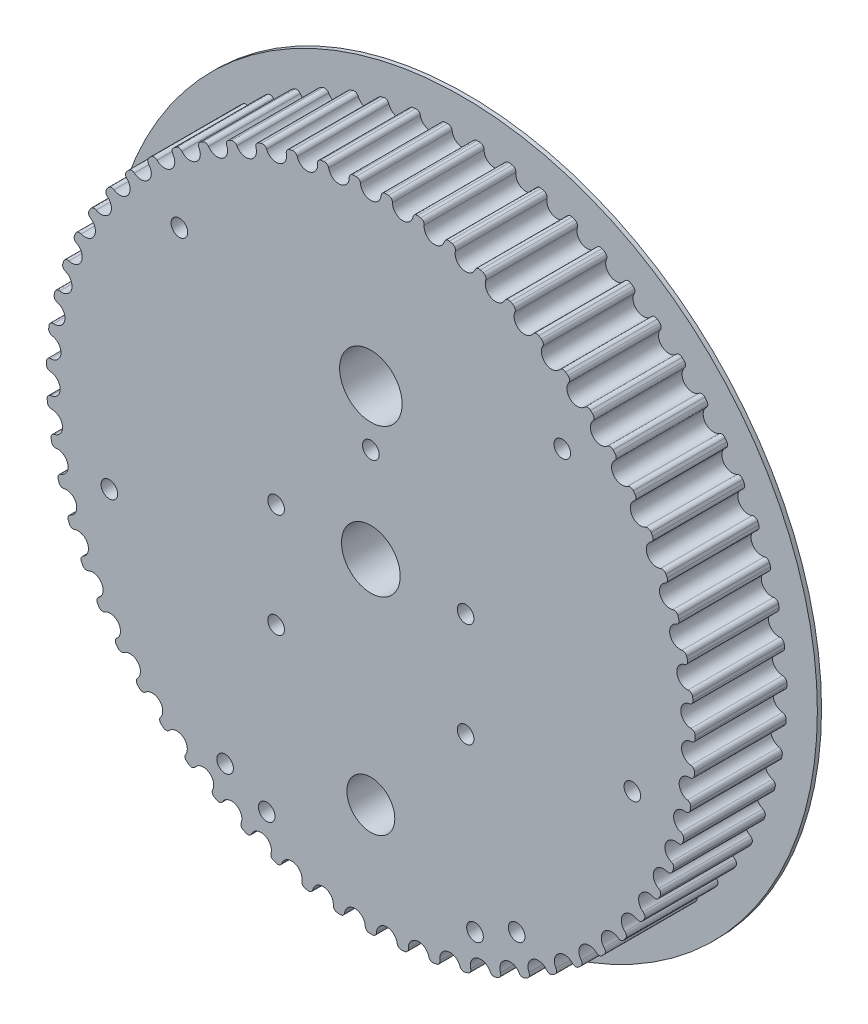
SolidWorks part; units mm, degrees
material "PETG"
ref_plane "Front Plane" through (0, 0, 0) normal (0, 0, 1) x (1, 0, 0)
ref_plane "Top Plane" through (0, 0, 0) normal (0, 1, 0) x (1, 0, 0)
ref_plane "Right Plane" through (0, 0, 0) normal (1, 0, 0) x (0, 0, -1)
sketch "Sketch1" plane through (0, 0, 0) normal (0, 0, 1) x (1, 0, 0)
  line L0 (0, 0) -> (0, 50000) construction
  line L1 (0, 0) -> (3.9983, 80.1144) construction
  line L2 (0, 0) -> (-3.9983, 80.1144) construction
  circle A0 centre (0, 0) radius 80.2141 construction
  arc A1 (-2.4815, 76.9081) -> (2.4815, 76.9081) centre (0, 77.1141) ccw
  arc A2 (3.8832, 77.8073) -> (-3.8832, 77.8073) centre (0, 0) ccw construction
  arc A3 (-2.4815, 76.9081) -> (-3.5233, 77.8244) centre (-3.478, 76.8254) ccw
  arc A4 (3.5233, 77.8244) -> (2.4815, 76.9081) centre (3.478, 76.8254) ccw
  arc A5 (-3.5233, 77.8244) -> (-3.8832, 77.8073) centre (0, 0) ccw
  arc A6 (3.5233, 77.8244) -> (3.8832, 77.8073) centre (0, 0) cw
  arc A7 (4.243, 77.7885) -> (3.8832, 77.8073) centre (0, 0) ccw
  arc A8 (5.1884, 76.773) -> (4.243, 77.7885) centre (4.1886, 76.7899) ccw
  arc A9 (5.1884, 76.773) -> (10.1267, 76.2789) centre (7.6781, 76.7309) ccw
  arc A10 (11.2546, 77.0868) -> (10.1267, 76.2789) centre (11.1101, 76.0973) ccw
  arc A11 (11.2546, 77.0868) -> (11.611, 77.034) centre (0, 0) cw
  arc A12 (11.9672, 76.9794) -> (11.611, 77.034) centre (0, 0) ccw
  arc A13 (12.8068, 75.8749) -> (11.9672, 76.9794) centre (11.8136, 75.9913) ccw
  arc A14 (12.8068, 75.8749) -> (17.6713, 74.8915) centre (15.2799, 75.5851) ccw
  arc A15 (18.874, 75.5832) -> (17.6713, 74.8915) centre (18.6317, 74.613) ccw
  arc A16 (18.874, 75.5832) -> (19.2234, 75.4951) centre (0, 0) cw
  arc A17 (19.5724, 75.4054) -> (19.2234, 75.4951) centre (0, 0) ccw
  arc A18 (20.2978, 74.2227) -> (19.5724, 75.4054) centre (19.3212, 74.4374) ccw
  arc A19 (20.2978, 74.2227) -> (25.0403, 72.7599) centre (22.7298, 73.6881) ccw
  arc A20 (26.3059, 73.3284) -> (25.0403, 72.7599) centre (25.9682, 72.3871) ccw
  arc A21 (26.3059, 73.3284) -> (26.6448, 73.2059) centre (0, 0) cw
  arc A22 (26.9831, 73.0819) -> (26.6448, 73.2059) centre (0, 0) ccw
  arc A23 (27.5872, 71.8329) -> (26.9831, 73.0819) centre (26.6367, 72.1438) ccw
  arc A24 (27.5872, 71.8329) -> (32.1604, 69.9051) centre (29.9538, 71.0588) ccw
  arc A25 (33.4763, 70.3448) -> (32.1604, 69.9051) centre (33.0466, 69.4418) ccw
  arc A26 (33.4763, 70.3448) -> (33.8013, 70.1892) centre (0, 0) cw
  arc A27 (34.1256, 70.0321) -> (33.8013, 70.1892) centre (0, 0) ccw
  arc A28 (34.6023, 68.7291) -> (34.1256, 70.0321) centre (33.6876, 69.1331) ccw
  arc A29 (34.6023, 68.7291) -> (38.9609, 66.3556) centre (36.8801, 67.7233) ccw
  arc A30 (40.314, 66.662) -> (38.9609, 66.3556) centre (39.7965, 65.8063) ccw
  arc A31 (40.314, 66.662) -> (40.6219, 66.4749) centre (0, 0) cw
  arc A32 (40.929, 66.2862) -> (40.6219, 66.4749) centre (0, 0) ccw
  arc A33 (41.2736, 64.9423) -> (40.929, 66.2862) centre (40.4036, 65.4354) ccw
  arc A34 (41.2736, 64.9423) -> (45.3742, 62.1466) centre (43.4399, 63.7147) ccw
  arc A35 (46.7511, 62.3168) -> (45.3742, 62.1466) centre (46.151, 61.5169) ccw
  arc A36 (46.7511, 62.3168) -> (47.0388, 62.0999) centre (0, 0) cw
  arc A37 (47.3256, 61.8816) -> (47.0388, 62.0999) centre (0, 0) ccw
  arc A38 (47.5347, 60.5101) -> (47.3256, 61.8816) centre (46.7181, 61.0873) ccw
  arc A39 (47.5347, 60.5101) -> (51.3365, 57.32) centre (49.568, 59.0728) ccw
  arc A40 (52.7235, 57.3522) -> (51.3365, 57.32) centre (52.0467, 56.616) ccw
  arc A41 (52.7235, 57.3522) -> (52.9882, 57.1077) centre (0, 0) cw
  arc A42 (53.2518, 56.862) -> (52.9882, 57.1077) centre (0, 0) ccw
  arc A43 (53.3233, 55.4765) -> (53.2518, 56.862) centre (52.5683, 56.1321) ccw
  arc A44 (53.3233, 55.4765) -> (56.7886, 51.9237) centre (55.2034, 53.8439) ccw
  arc A45 (58.172, 51.8177) -> (56.7886, 51.9237) centre (57.4253, 51.1525) ccw
  arc A46 (58.172, 51.8177) -> (58.411, 51.548) centre (0, 0) cw
  arc A47 (58.6488, 51.2773) -> (58.411, 51.548) centre (0, 0) ccw
  arc A48 (58.582, 49.8915) -> (58.6488, 51.2773) centre (57.896, 50.6191) ccw
  arc A49 (58.582, 49.8915) -> (61.6764, 46.0113) centre (60.2902, 48.0798) ccw
  arc A50 (63.0423, 45.7681) -> (61.6764, 46.0113) centre (62.233, 45.1806) ccw
  arc A51 (63.0423, 45.7681) -> (63.2533, 45.476) centre (0, 0) cw
  arc A52 (63.463, 45.183) -> (63.2533, 45.476) centre (0, 0) ccw
  arc A53 (63.2585, 43.8107) -> (63.463, 45.183) centre (62.6483, 44.603) ccw
  arc A54 (63.2585, 43.8107) -> (65.9511, 39.6417) centre (64.7778, 41.838) ccw
  arc A55 (67.286, 39.2637) -> (65.9511, 39.6417) centre (66.4223, 38.7597) ccw
  arc A56 (67.286, 39.2637) -> (67.4669, 38.952) centre (0, 0) cw
  arc A57 (67.6464, 38.6396) -> (67.4669, 38.952) centre (0, 0) ccw
  arc A58 (67.3063, 37.2945) -> (67.6464, 38.6396) centre (66.778, 38.1436) ccw
  arc A59 (67.3063, 37.2945) -> (69.5704, 32.8781) centre (68.6217, 35.1803) ccw
  arc A60 (70.8611, 32.3691) -> (69.5704, 32.8781) centre (69.9515, 31.9536) ccw
  arc A61 (70.8611, 32.3691) -> (71.01, 32.0409) centre (0, 0) cw
  arc A62 (71.1575, 31.7122) -> (71.01, 32.0409) centre (0, 0) ccw
  arc A63 (70.6852, 30.4076) -> (71.1575, 31.7122) centre (70.2441, 31.3051) ccw
  arc A64 (70.6852, 30.4076) -> (72.4983, 25.7878) centre (71.7835, 28.1729) ccw
  arc A65 (73.7319, 25.1527) -> (72.4983, 25.7878) centre (72.7854, 24.8299) ccw
  arc A66 (73.7319, 25.1527) -> (73.8474, 24.8114) centre (0, 0) cw
  arc A67 (73.9614, 24.4696) -> (73.8474, 24.8114) centre (0, 0) ccw
  arc A68 (73.3615, 23.2186) -> (73.9614, 24.4696) centre (73.012, 24.1555) ccw
  arc A69 (73.3615, 23.2186) -> (74.7057, 18.4411) centre (74.2319, 20.8856) ccw
  arc A70 (75.8699, 17.6864) -> (74.7057, 18.4411) centre (74.896, 17.4594) ccw
  arc A71 (75.8699, 17.6864) -> (75.9509, 17.3353) centre (0, 0) cw
  arc A72 (76.0302, 16.9838) -> (75.9509, 17.3353) centre (0, 0) ccw
  arc A73 (75.3088, 15.7987) -> (76.0302, 16.9838) centre (75.0543, 16.7658) ccw
  arc A74 (75.3088, 15.7987) -> (76.1706, 10.9112) centre (75.9426, 13.3907) ccw
  arc A75 (77.2539, 10.0443) -> (76.1706, 10.9112) centre (76.2622, 9.9154) ccw
  arc A76 (77.2539, 10.0443) -> (77.2995, 9.6869) centre (0, 0) cw
  arc A77 (77.3435, 9.3292) -> (77.2995, 9.6869) centre (0, 0) ccw
  arc A78 (76.5076, 8.2219) -> (77.3435, 9.3292) centre (76.3507, 9.2095) ccw
  arc A79 (76.5076, 8.2219) -> (76.8785, 3.2728) centre (76.8985, 5.7627) ccw
  arc A80 (77.8701, 2.3024) -> (76.8785, 3.2728) centre (76.8705, 2.2729) ccw
  arc A81 (77.8701, 2.3024) -> (77.8799, 1.9422) centre (0, 0) cw
  arc A82 (77.888, 1.582) -> (77.8799, 1.9422) centre (0, 0) ccw
  arc A83 (76.9461, 0.5633) -> (77.888, 1.582) centre (76.8882, 1.5616) ccw
  arc A84 (76.9461, 0.5633) -> (76.8224, -4.3981) centre (77.0901, -1.9225) ccw
  arc A85 (77.7124, -5.4624) -> (76.8224, -4.3981) centre (76.7148, -5.3923) ccw
  arc A86 (77.7124, -5.4624) -> (77.6863, -5.8218) centre (0, 0) cw
  arc A87 (77.6585, -6.181) -> (77.6863, -5.8218) centre (0, 0) ccw
  arc A88 (76.6198, -7.1008) -> (77.6585, -6.181) centre (76.6616, -6.1017) ccw
  arc A89 (76.6198, -7.1008) -> (76.0027, -12.0252) centre (76.5156, -9.5887) ccw
  arc A90 (76.7823, -13.1729) -> (76.0027, -12.0252) centre (75.7967, -13.0038) ccw
  arc A91 (76.7823, -13.1729) -> (76.7206, -13.5279) centre (0, 0) cw
  arc A92 (76.6572, -13.8826) -> (76.7206, -13.5279) centre (0, 0) ccw
  arc A93 (75.5321, -14.6944) -> (76.6572, -13.8826) centre (75.6732, -13.7044) ccw
  arc A94 (75.5321, -14.6944) -> (74.4277, -19.5329) centre (75.1807, -17.1595) ccw
  arc A95 (75.0892, -20.7525) -> (74.4277, -19.5329) centre (74.1253, -20.4861) ccw
  arc A96 (75.0892, -20.7525) -> (74.9924, -21.0996) centre (0, 0) cw
  arc A97 (74.894, -21.4462) -> (74.9924, -21.0996) centre (0, 0) ccw
  arc A98 (73.6936, -22.142) -> (74.894, -21.4462) centre (73.9326, -21.1709) ccw
  arc A99 (73.6936, -22.142) -> (72.113, -26.8465) centre (73.0986, -24.5598) ccw
  arc A100 (72.6497, -28.1258) -> (72.113, -26.8465) centre (71.7172, -27.7648) ccw
  arc A101 (72.6497, -28.1258) -> (72.5189, -28.4616) centre (0, 0) cw
  arc A102 (72.3865, -28.7967) -> (72.5189, -28.4616) centre (0, 0) ccw
  arc A103 (71.1228, -29.3694) -> (72.3865, -28.7967) centre (71.4573, -28.427) ccw
  arc A104 (71.1228, -29.3694) -> (69.0816, -33.8932) centre (70.2899, -31.716) ccw
  arc A105 (69.4883, -35.2196) -> (69.0816, -33.8932) centre (68.5963, -34.7676) ccw
  arc A106 (69.4883, -35.2196) -> (69.3247, -35.5407) centre (0, 0) cw
  arc A107 (69.1595, -35.861) -> (69.3247, -35.5407) centre (0, 0) ccw
  arc A108 (67.8451, -36.305) -> (69.1595, -35.861) centre (68.2718, -35.4006) ccw
  arc A109 (67.8451, -36.305) -> (65.3637, -40.6031) centre (66.7828, -38.557) ccw
  arc A110 (65.6363, -41.9634) -> (65.3637, -40.6031) centre (64.7937, -41.4248) ccw
  arc A111 (65.6363, -41.9634) -> (65.4415, -42.2666) centre (0, 0) cw
  arc A112 (65.2453, -42.5688) -> (65.4415, -42.2666) centre (0, 0) ccw
  arc A113 (63.8932, -42.8798) -> (65.2453, -42.5688) centre (64.4077, -42.0224) ccw
  arc A114 (63.8932, -42.8798) -> (60.9961, -46.9094) centre (62.6119, -45.0149) ccw
  arc A115 (61.1319, -48.2902) -> (60.9961, -46.9094) centre (60.3472, -47.6703) ccw
  arc A116 (61.1319, -48.2902) -> (60.9079, -48.5724) centre (0, 0) cw
  arc A117 (60.6826, -48.8536) -> (60.9079, -48.5724) centre (0, 0) ccw
  arc A118 (59.3062, -49.0285) -> (60.6826, -48.8536) centre (59.9036, -48.2265) ccw
  arc A119 (59.3062, -49.0285) -> (56.0223, -52.7496) centre (57.8187, -51.0253) ccw
  arc A120 (56.02, -54.137) -> (56.0223, -52.7496) centre (55.3009, -53.442) ccw
  arc A121 (56.02, -54.137) -> (55.769, -54.3955) centre (0, 0) cw
  arc A122 (55.5168, -54.6529) -> (55.769, -54.3955) centre (0, 0) ccw
  arc A123 (54.1299, -54.6898) -> (55.5168, -54.6529) centre (54.8041, -53.9513) ccw
  arc A124 (54.1299, -54.6898) -> (50.4918, -58.0655) centre (52.4509, -56.5286) ccw
  arc A125 (50.3513, -59.4457) -> (50.4918, -58.0655) centre (49.705, -58.6827) ccw
  arc A126 (50.3513, -59.4457) -> (50.0758, -59.678) centre (0, 0) cw
  arc A127 (49.7992, -59.909) -> (50.0758, -59.678) centre (0, 0) ccw
  arc A128 (48.4155, -59.8076) -> (49.7992, -59.909) centre (49.16, -59.14) ccw
  arc A129 (48.4155, -59.8076) -> (44.4594, -62.8043) centre (46.5618, -61.4701) ccw
  arc A130 (44.1822, -64.1637) -> (44.4594, -62.8043) centre (43.6151, -63.3401) ccw
  arc A131 (44.1822, -64.1637) -> (43.8849, -64.3674) centre (0, 0) cw
  arc A132 (43.5867, -64.5697) -> (43.8849, -64.3674) centre (0, 0) ccw
  arc A133 (42.22, -64.3311) -> (43.5867, -64.5697) centre (43.0272, -63.7408) ccw
  arc A134 (42.22, -64.3311) -> (37.9852, -66.9189) centre (40.21, -65.8008) ccw
  arc A135 (37.574, -68.244) -> (37.9852, -66.9189) centre (37.0917, -67.368) ccw
  arc A136 (37.574, -68.244) -> (37.2579, -68.4171) centre (0, 0) cw
  arc A137 (36.9411, -68.5887) -> (37.2579, -68.4171) centre (0, 0) ccw
  arc A138 (35.6049, -68.2152) -> (36.9411, -68.5887) centre (36.4669, -67.7082) ccw
  arc A139 (35.6049, -68.2152) -> (31.1335, -70.3685) centre (33.4586, -69.4774) ccw
  arc A140 (30.5924, -71.646) -> (31.1335, -70.3685) centre (30.1997, -70.7264) ccw
  arc A141 (30.5924, -71.646) -> (30.2607, -71.7868) centre (0, 0) cw
  arc A142 (29.9283, -71.926) -> (30.2607, -71.7868) centre (0, 0) ccw
  arc A143 (28.6359, -71.4213) -> (29.9283, -71.926) centre (29.5441, -71.0027) ccw
  arc A144 (28.6359, -71.4213) -> (23.9723, -73.1187) centre (26.3746, -72.4635) ccw
  arc A145 (23.3067, -74.336) -> (23.9723, -73.1187) centre (23.0075, -73.3818) ccw
  arc A146 (23.3067, -74.336) -> (22.9626, -74.443) centre (0, 0) cw
  arc A147 (22.6181, -74.5484) -> (22.9626, -74.443) centre (0, 0) ccw
  arc A148 (21.3824, -73.9176) -> (22.6181, -74.5484) centre (22.3277, -73.5915) ccw
  arc A149 (21.3824, -73.9176) -> (16.5729, -75.1422) centre (19.0285, -74.7295) ccw
  arc A150 (15.7894, -76.2872) -> (16.5729, -75.1422) centre (15.5867, -75.308) ccw
  arc A151 (15.7894, -76.2872) -> (15.4364, -76.3594) centre (0, 0) cw
  arc A152 (15.083, -76.43) -> (15.4364, -76.3594) centre (0, 0) ccw
  arc A153 (13.9163, -75.6793) -> (15.083, -76.43) centre (14.8894, -75.449) ccw
  arc A154 (13.9163, -75.6793) -> (9.0088, -76.419) centre (11.4933, -76.2528) ccw
  arc A155 (8.1152, -77.4803) -> (9.0088, -76.419) centre (8.011, -76.4857) ccw
  arc A156 (8.1152, -77.4803) -> (7.7567, -77.517) centre (0, 0) cw
  arc A157 (7.3981, -77.552) -> (7.7567, -77.517) centre (0, 0) ccw
  arc A158 (6.3119, -76.6888) -> (7.3981, -77.552) centre (7.3031, -76.5565) ccw
  arc A159 (6.3119, -76.6888) -> (1.3552, -76.9362) centre (3.8438, -77.0182) ccw
  arc A160 (0.3603, -77.9033) -> (1.3552, -76.9362) centre (0.3557, -76.9033) ccw
  arc A161 (0.3603, -77.9033) -> (0, -77.9041) centre (0, 0) cw
  arc A162 (-0.3603, -77.9033) -> (0, -77.9041) centre (0, 0) ccw
  arc A163 (-1.3552, -76.9362) -> (-0.3603, -77.9033) centre (-0.3557, -76.9033) ccw
  arc A164 (-1.3552, -76.9362) -> (-6.3119, -76.6888) centre (-3.8438, -77.0182) ccw
  arc A165 (-7.3981, -77.552) -> (-6.3119, -76.6888) centre (-7.3031, -76.5565) ccw
  arc A166 (-7.3981, -77.552) -> (-7.7567, -77.517) centre (0, 0) cw
  arc A167 (-8.1152, -77.4803) -> (-7.7567, -77.517) centre (0, 0) ccw
  arc A168 (-9.0088, -76.419) -> (-8.1152, -77.4803) centre (-8.011, -76.4857) ccw
  arc A169 (-9.0088, -76.419) -> (-13.9163, -75.6793) centre (-11.4933, -76.2528) ccw
  arc A170 (-15.083, -76.43) -> (-13.9163, -75.6793) centre (-14.8894, -75.449) ccw
  arc A171 (-15.083, -76.43) -> (-15.4364, -76.3594) centre (0, 0) cw
  arc A172 (-15.7894, -76.2872) -> (-15.4364, -76.3594) centre (0, 0) ccw
  arc A173 (-16.5729, -75.1422) -> (-15.7894, -76.2872) centre (-15.5867, -75.308) ccw
  arc A174 (-16.5729, -75.1422) -> (-21.3824, -73.9176) centre (-19.0285, -74.7295) ccw
  arc A175 (-22.6181, -74.5484) -> (-21.3824, -73.9176) centre (-22.3277, -73.5915) ccw
  arc A176 (-22.6181, -74.5484) -> (-22.9626, -74.443) centre (0, 0) cw
  arc A177 (-23.3067, -74.336) -> (-22.9626, -74.443) centre (0, 0) ccw
  arc A178 (-23.9723, -73.1187) -> (-23.3067, -74.336) centre (-23.0075, -73.3818) ccw
  arc A179 (-23.9723, -73.1187) -> (-28.6359, -71.4213) centre (-26.3746, -72.4635) ccw
  arc A180 (-29.9283, -71.926) -> (-28.6359, -71.4213) centre (-29.5441, -71.0027) ccw
  arc A181 (-29.9283, -71.926) -> (-30.2607, -71.7868) centre (0, 0) cw
  arc A182 (-30.5924, -71.646) -> (-30.2607, -71.7868) centre (0, 0) ccw
  arc A183 (-31.1335, -70.3685) -> (-30.5924, -71.646) centre (-30.1997, -70.7264) ccw
  arc A184 (-31.1335, -70.3685) -> (-35.6049, -68.2152) centre (-33.4586, -69.4774) ccw
  arc A185 (-36.9411, -68.5887) -> (-35.6049, -68.2152) centre (-36.4669, -67.7082) ccw
  arc A186 (-36.9411, -68.5887) -> (-37.2579, -68.4171) centre (0, 0) cw
  arc A187 (-37.574, -68.244) -> (-37.2579, -68.4171) centre (0, 0) ccw
  arc A188 (-37.9852, -66.9189) -> (-37.574, -68.244) centre (-37.0917, -67.368) ccw
  arc A189 (-37.9852, -66.9189) -> (-42.22, -64.3311) centre (-40.21, -65.8008) ccw
  arc A190 (-43.5867, -64.5697) -> (-42.22, -64.3311) centre (-43.0272, -63.7408) ccw
  arc A191 (-43.5867, -64.5697) -> (-43.8849, -64.3674) centre (0, 0) cw
  arc A192 (-44.1822, -64.1637) -> (-43.8849, -64.3674) centre (0, 0) ccw
  arc A193 (-44.4594, -62.8043) -> (-44.1822, -64.1637) centre (-43.6151, -63.3401) ccw
  arc A194 (-44.4594, -62.8043) -> (-48.4155, -59.8076) centre (-46.5618, -61.4701) ccw
  arc A195 (-49.7992, -59.909) -> (-48.4155, -59.8076) centre (-49.16, -59.14) ccw
  arc A196 (-49.7992, -59.909) -> (-50.0758, -59.678) centre (0, 0) cw
  arc A197 (-50.3513, -59.4457) -> (-50.0758, -59.678) centre (0, 0) ccw
  arc A198 (-50.4918, -58.0655) -> (-50.3513, -59.4457) centre (-49.705, -58.6827) ccw
  arc A199 (-50.4918, -58.0655) -> (-54.1299, -54.6898) centre (-52.4509, -56.5286) ccw
  arc A200 (-55.5168, -54.6529) -> (-54.1299, -54.6898) centre (-54.8041, -53.9513) ccw
  arc A201 (-55.5168, -54.6529) -> (-55.769, -54.3955) centre (0, 0) cw
  arc A202 (-56.02, -54.137) -> (-55.769, -54.3955) centre (0, 0) ccw
  arc A203 (-56.0223, -52.7496) -> (-56.02, -54.137) centre (-55.3009, -53.442) ccw
  arc A204 (-56.0223, -52.7496) -> (-59.3062, -49.0285) centre (-57.8187, -51.0253) ccw
  arc A205 (-60.6826, -48.8536) -> (-59.3062, -49.0285) centre (-59.9036, -48.2265) ccw
  arc A206 (-60.6826, -48.8536) -> (-60.9079, -48.5724) centre (0, 0) cw
  arc A207 (-61.1319, -48.2902) -> (-60.9079, -48.5724) centre (0, 0) ccw
  arc A208 (-60.9961, -46.9094) -> (-61.1319, -48.2902) centre (-60.3472, -47.6703) ccw
  arc A209 (-60.9961, -46.9094) -> (-63.8932, -42.8798) centre (-62.6119, -45.0149) ccw
  arc A210 (-65.2453, -42.5688) -> (-63.8932, -42.8798) centre (-64.4077, -42.0224) ccw
  arc A211 (-65.2453, -42.5688) -> (-65.4415, -42.2666) centre (0, 0) cw
  arc A212 (-65.6363, -41.9634) -> (-65.4415, -42.2666) centre (0, 0) ccw
  arc A213 (-65.3637, -40.6031) -> (-65.6363, -41.9634) centre (-64.7937, -41.4248) ccw
  arc A214 (-65.3637, -40.6031) -> (-67.8451, -36.305) centre (-66.7828, -38.557) ccw
  arc A215 (-69.1595, -35.861) -> (-67.8451, -36.305) centre (-68.2718, -35.4006) ccw
  arc A216 (-69.1595, -35.861) -> (-69.3247, -35.5407) centre (0, 0) cw
  arc A217 (-69.4883, -35.2196) -> (-69.3247, -35.5407) centre (0, 0) ccw
  arc A218 (-69.0816, -33.8932) -> (-69.4883, -35.2196) centre (-68.5963, -34.7676) ccw
  arc A219 (-69.0816, -33.8932) -> (-71.1228, -29.3694) centre (-70.2899, -31.716) ccw
  arc A220 (-72.3865, -28.7967) -> (-71.1228, -29.3694) centre (-71.4573, -28.427) ccw
  arc A221 (-72.3865, -28.7967) -> (-72.5189, -28.4616) centre (0, 0) cw
  arc A222 (-72.6497, -28.1258) -> (-72.5189, -28.4616) centre (0, 0) ccw
  arc A223 (-72.113, -26.8465) -> (-72.6497, -28.1258) centre (-71.7172, -27.7648) ccw
  arc A224 (-72.113, -26.8465) -> (-73.6936, -22.142) centre (-73.0986, -24.5598) ccw
  arc A225 (-74.894, -21.4462) -> (-73.6936, -22.142) centre (-73.9326, -21.1709) ccw
  arc A226 (-74.894, -21.4462) -> (-74.9924, -21.0996) centre (0, 0) cw
  arc A227 (-75.0892, -20.7525) -> (-74.9924, -21.0996) centre (0, 0) ccw
  arc A228 (-74.4277, -19.5329) -> (-75.0892, -20.7525) centre (-74.1253, -20.4861) ccw
  arc A229 (-74.4277, -19.5329) -> (-75.5321, -14.6944) centre (-75.1807, -17.1595) ccw
  arc A230 (-76.6572, -13.8826) -> (-75.5321, -14.6944) centre (-75.6732, -13.7044) ccw
  arc A231 (-76.6572, -13.8826) -> (-76.7206, -13.5279) centre (0, 0) cw
  arc A232 (-76.7823, -13.1729) -> (-76.7206, -13.5279) centre (0, 0) ccw
  arc A233 (-76.0027, -12.0252) -> (-76.7823, -13.1729) centre (-75.7967, -13.0038) ccw
  arc A234 (-76.0027, -12.0252) -> (-76.6198, -7.1008) centre (-76.5156, -9.5887) ccw
  arc A235 (-77.6585, -6.181) -> (-76.6198, -7.1008) centre (-76.6616, -6.1017) ccw
  arc A236 (-77.6585, -6.181) -> (-77.6863, -5.8218) centre (0, 0) cw
  arc A237 (-77.7124, -5.4624) -> (-77.6863, -5.8218) centre (0, 0) ccw
  arc A238 (-76.8224, -4.3981) -> (-77.7124, -5.4624) centre (-76.7148, -5.3923) ccw
  arc A239 (-76.8224, -4.3981) -> (-76.9461, 0.5633) centre (-77.0901, -1.9225) ccw
  arc A240 (-77.888, 1.582) -> (-76.9461, 0.5633) centre (-76.8882, 1.5616) ccw
  arc A241 (-77.888, 1.582) -> (-77.8799, 1.9422) centre (0, 0) cw
  arc A242 (-77.8701, 2.3024) -> (-77.8799, 1.9422) centre (0, 0) ccw
  arc A243 (-76.8785, 3.2728) -> (-77.8701, 2.3024) centre (-76.8705, 2.2729) ccw
  arc A244 (-76.8785, 3.2728) -> (-76.5076, 8.2219) centre (-76.8985, 5.7627) ccw
  arc A245 (-77.3435, 9.3292) -> (-76.5076, 8.2219) centre (-76.3507, 9.2095) ccw
  arc A246 (-77.3435, 9.3292) -> (-77.2995, 9.6869) centre (0, 0) cw
  arc A247 (-77.2539, 10.0443) -> (-77.2995, 9.6869) centre (0, 0) ccw
  arc A248 (-76.1706, 10.9112) -> (-77.2539, 10.0443) centre (-76.2622, 9.9154) ccw
  arc A249 (-76.1706, 10.9112) -> (-75.3088, 15.7987) centre (-75.9426, 13.3907) ccw
  arc A250 (-76.0302, 16.9838) -> (-75.3088, 15.7987) centre (-75.0543, 16.7658) ccw
  arc A251 (-76.0302, 16.9838) -> (-75.9509, 17.3353) centre (0, 0) cw
  arc A252 (-75.8699, 17.6864) -> (-75.9509, 17.3353) centre (0, 0) ccw
  arc A253 (-74.7057, 18.4411) -> (-75.8699, 17.6864) centre (-74.896, 17.4594) ccw
  arc A254 (-74.7057, 18.4411) -> (-73.3615, 23.2186) centre (-74.2319, 20.8856) ccw
  arc A255 (-73.9614, 24.4696) -> (-73.3615, 23.2186) centre (-73.012, 24.1555) ccw
  arc A256 (-73.9614, 24.4696) -> (-73.8474, 24.8114) centre (0, 0) cw
  arc A257 (-73.7319, 25.1527) -> (-73.8474, 24.8114) centre (0, 0) ccw
  arc A258 (-72.4983, 25.7878) -> (-73.7319, 25.1527) centre (-72.7854, 24.8299) ccw
  arc A259 (-72.4983, 25.7878) -> (-70.6852, 30.4076) centre (-71.7835, 28.1729) ccw
  arc A260 (-71.1575, 31.7122) -> (-70.6852, 30.4076) centre (-70.2441, 31.3051) ccw
  arc A261 (-71.1575, 31.7122) -> (-71.01, 32.0409) centre (0, 0) cw
  arc A262 (-70.8611, 32.3691) -> (-71.01, 32.0409) centre (0, 0) ccw
  arc A263 (-69.5704, 32.8781) -> (-70.8611, 32.3691) centre (-69.9515, 31.9536) ccw
  arc A264 (-69.5704, 32.8781) -> (-67.3063, 37.2945) centre (-68.6217, 35.1803) ccw
  arc A265 (-67.6464, 38.6396) -> (-67.3063, 37.2945) centre (-66.778, 38.1436) ccw
  arc A266 (-67.6464, 38.6396) -> (-67.4669, 38.952) centre (0, 0) cw
  arc A267 (-67.286, 39.2637) -> (-67.4669, 38.952) centre (0, 0) ccw
  arc A268 (-65.9511, 39.6417) -> (-67.286, 39.2637) centre (-66.4223, 38.7597) ccw
  arc A269 (-65.9511, 39.6417) -> (-63.2585, 43.8107) centre (-64.7778, 41.838) ccw
  arc A270 (-63.463, 45.183) -> (-63.2585, 43.8107) centre (-62.6483, 44.603) ccw
  arc A271 (-63.463, 45.183) -> (-63.2533, 45.476) centre (0, 0) cw
  arc A272 (-63.0423, 45.7681) -> (-63.2533, 45.476) centre (0, 0) ccw
  arc A273 (-61.6764, 46.0113) -> (-63.0423, 45.7681) centre (-62.233, 45.1806) ccw
  arc A274 (-61.6764, 46.0113) -> (-58.582, 49.8915) centre (-60.2902, 48.0798) ccw
  arc A275 (-58.6488, 51.2773) -> (-58.582, 49.8915) centre (-57.896, 50.6191) ccw
  arc A276 (-58.6488, 51.2773) -> (-58.411, 51.548) centre (0, 0) cw
  arc A277 (-58.172, 51.8177) -> (-58.411, 51.548) centre (0, 0) ccw
  arc A278 (-56.7886, 51.9237) -> (-58.172, 51.8177) centre (-57.4253, 51.1525) ccw
  arc A279 (-56.7886, 51.9237) -> (-53.3233, 55.4765) centre (-55.2034, 53.8439) ccw
  arc A280 (-53.2518, 56.862) -> (-53.3233, 55.4765) centre (-52.5683, 56.1321) ccw
  arc A281 (-53.2518, 56.862) -> (-52.9882, 57.1077) centre (0, 0) cw
  arc A282 (-52.7235, 57.3522) -> (-52.9882, 57.1077) centre (0, 0) ccw
  arc A283 (-51.3365, 57.32) -> (-52.7235, 57.3522) centre (-52.0467, 56.616) ccw
  arc A284 (-51.3365, 57.32) -> (-47.5347, 60.5101) centre (-49.568, 59.0728) ccw
  arc A285 (-47.3256, 61.8816) -> (-47.5347, 60.5101) centre (-46.7181, 61.0873) ccw
  arc A286 (-47.3256, 61.8816) -> (-47.0388, 62.0999) centre (0, 0) cw
  arc A287 (-46.7511, 62.3168) -> (-47.0388, 62.0999) centre (0, 0) ccw
  arc A288 (-45.3742, 62.1466) -> (-46.7511, 62.3168) centre (-46.151, 61.5169) ccw
  arc A289 (-45.3742, 62.1466) -> (-41.2736, 64.9423) centre (-43.4399, 63.7147) ccw
  arc A290 (-40.929, 66.2862) -> (-41.2736, 64.9423) centre (-40.4036, 65.4354) ccw
  arc A291 (-40.929, 66.2862) -> (-40.6219, 66.4749) centre (0, 0) cw
  arc A292 (-40.314, 66.662) -> (-40.6219, 66.4749) centre (0, 0) ccw
  arc A293 (-38.9609, 66.3556) -> (-40.314, 66.662) centre (-39.7965, 65.8063) ccw
  arc A294 (-38.9609, 66.3556) -> (-34.6023, 68.7291) centre (-36.8801, 67.7233) ccw
  arc A295 (-34.1256, 70.0321) -> (-34.6023, 68.7291) centre (-33.6876, 69.1331) ccw
  arc A296 (-34.1256, 70.0321) -> (-33.8013, 70.1892) centre (0, 0) cw
  arc A297 (-33.4763, 70.3448) -> (-33.8013, 70.1892) centre (0, 0) ccw
  arc A298 (-32.1604, 69.9051) -> (-33.4763, 70.3448) centre (-33.0466, 69.4418) ccw
  arc A299 (-32.1604, 69.9051) -> (-27.5872, 71.8329) centre (-29.9538, 71.0588) ccw
  arc A300 (-26.9831, 73.0819) -> (-27.5872, 71.8329) centre (-26.6367, 72.1438) ccw
  arc A301 (-26.9831, 73.0819) -> (-26.6448, 73.2059) centre (0, 0) cw
  arc A302 (-26.3059, 73.3284) -> (-26.6448, 73.2059) centre (0, 0) ccw
  arc A303 (-25.0403, 72.7599) -> (-26.3059, 73.3284) centre (-25.9682, 72.3871) ccw
  arc A304 (-25.0403, 72.7599) -> (-20.2978, 74.2227) centre (-22.7298, 73.6881) ccw
  arc A305 (-19.5724, 75.4054) -> (-20.2978, 74.2227) centre (-19.3212, 74.4374) ccw
  arc A306 (-19.5724, 75.4054) -> (-19.2234, 75.4951) centre (0, 0) cw
  arc A307 (-18.874, 75.5832) -> (-19.2234, 75.4951) centre (0, 0) ccw
  arc A308 (-17.6713, 74.8915) -> (-18.874, 75.5832) centre (-18.6317, 74.613) ccw
  arc A309 (-17.6713, 74.8915) -> (-12.8068, 75.8749) centre (-15.2799, 75.5851) ccw
  arc A310 (-11.9672, 76.9794) -> (-12.8068, 75.8749) centre (-11.8136, 75.9913) ccw
  arc A311 (-11.9672, 76.9794) -> (-11.611, 77.034) centre (0, 0) cw
  arc A312 (-11.2546, 77.0868) -> (-11.611, 77.034) centre (0, 0) ccw
  arc A313 (-10.1267, 76.2789) -> (-11.2546, 77.0868) centre (-11.1101, 76.0973) ccw
  arc A314 (-10.1267, 76.2789) -> (-5.1884, 76.773) centre (-7.6781, 76.7309) ccw
  arc A315 (-4.243, 77.7885) -> (-5.1884, 76.773) centre (-4.1886, 76.7899) ccw
  arc A316 (-4.243, 77.7885) -> (-3.8832, 77.8073) centre (0, 0) cw
  point P9 (0, 74.6241)
  point P11 (0, 80.2141)
  point P12 (0, 77.9041)
  dimension "D1" = 160.4282
  dimension "D6" = 1
  dimension "D3" = 2.49
  dimension "D4" = 5.59
  dimension "D5" = 3.28
  dimension "D2" = 8
  dimension "D7" = 63
extrude "Boss-Extrude1" add sketch "Sketch1" along normal blind 22 contours A316 A315 A314 A313 A312 A311 A310 A309 A308 A307 A306 A305 A304 A303 A302 A301 A300 A299 A298 A297 A296 A295 A294 A293 A292 A291 A290 A289 A288 A287 A286 A285 A284 A283 A282 A281 A280 A279 A278 A277 A276 A275 A274 A273 A272 A271 A270 A269 A268 A267 A266 region at (0, 0, 0)
sketch "Sketch2" plane through (0, 0, 0) normal (0, 0, -1) x (-1, 0, 0)
  circle A0 centre (0, 0) radius 85.2141
  dimension "D1" = 170.4282
extrude "Boss-Extrude2" add sketch "Sketch2" along normal blind 1
sketch "Sketch3" plane through (0, 0, 22) normal (0, 0, 1) x (1, 0, 0)
  circle A0 centre (0, 0) radius 7.05
  circle A1 centre (0, -51.05) radius 5.75
  circle A2 centre (0, 36) radius 7.5
  dimension "D1" = 14.1
  dimension "D2" = 15
  dimension "D4" = 11.5
  dimension "D3" = 36
  dimension "D5" = 51.05
extrude "Cut-Extrude1" cut sketch "Sketch3" against normal through all
sketch "Sketch4" plane through (0, 0, 22) normal (0, 0, 1) x (1, 0, 0)
  line L0 (0, 0) -> (0, 50000) construction
  line L1 (0, 0) -> (-45.9619, 45.9619) construction
  line L2 (0, 0) -> (45.9619, 45.9619) construction
  line L3 (0, 0) -> (-62.7852, -16.8232) construction
  line L4 (0, 0) -> (62.7852, -16.8232) construction
  circle A0 centre (-45.9619, 45.9619) radius 2
  circle A1 centre (45.9619, 45.9619) radius 2
  circle A2 centre (-25, -65) radius 2
  circle A3 centre (25, -65) radius 2
  circle A4 centre (-62.7852, -16.8232) radius 2
  circle A5 centre (62.7852, -16.8232) radius 2
  circle A6 centre (-35, -60) radius 2
  circle A7 centre (35, -60) radius 2
  circle A8 centre (-22.75, 0) radius 2
  circle A9 centre (22.75, 0) radius 2
  circle A10 centre (0, 22.75) radius 2
  circle A11 centre (-22.75, -25) radius 2
  circle A12 centre (22.75, -25) radius 2
  point P30 (0, 0)
  point P31 (0, 0)
  point P32 (0, 0)
  dimension "D1" = 4
  dimension "D2" = 65
  dimension "D3" = 45
  dimension "D4" = 25
  dimension "D5" = 65
  dimension "D6" = 25
  dimension "D7" = 60
  dimension "D8" = 35
  dimension "D9" = 60
  dimension "D10" = 35
  dimension "D11" = 22.75
  dimension "D12" = 22.75
  dimension "D13" = 22.75
  dimension "D14" = 25
extrude "Cut-Extrude2" cut sketch "Sketch4" against normal blind 18
equation "\"tol_dia_id_intfc\" = 0.0500mm ' For hole diameters - Interference fit"
equation "\"tol_dia_id_slip\"  = 0.0750mm ' For hole diameters - Slip fit"
equation "\"tol_dia_id_clear\" = 0.1000mm ' For hole diameters - Clearance fit"
equation "\"tol_dia_od_intfc\" = 0.0500mm ' For shaft diameters - Interference fit"
equation "\"tol_dia_od_slip\"  = 0.0750mm ' For shaft diameters - Slip fit"
equation "\"tol_dia_od_clear\" = 0.1000mm ' For shaft diameters - Clearance fit"
equation "\"tol_general_intfc\"= 0.0250mm ' For general parts (Horiz) - Interference fit"
equation "\"tol_general_slip\" = 0.0375mm ' For general parts (Horiz) - Slip fit"
equation "\"tol_general_clear\"= 0.0500mm ' For general parts (Horiz) - Clearance fit"
equation "\"tol_layer_intfc\"  = 0.0250mm ' For all parts (Vert) - Interference fit"
equation "\"tol_layer_slip\"   = 0.0375mm ' For all parts (Vert) - Slip fit"
equation "\"tol_layer_clear\"  = 0.0500mm ' For all parts (Vert) - Clearance fit"
equation "\"tol_corner_rad\"   = 0.100mm ' For corners that fit into other parts"
equation "\"pitch\"= 8mm"
equation "\"n\"= 63"
equation "\"pitch_dia\"= \"pitch\" * \"n\" / PI"
equation "\"belt_width\"= 22mm"
equation "\"D1@Sketch1\"=\"pitch_dia\""
equation "\"D2@Sketch1\"=\"pitch\""
equation "\"D7@Sketch1\"=\"n\""
equation "\"D1@Extrude-Thin2\"=\"belt_width\""
equation "\"D1@Boss-Extrude1\"=\"belt_width\""
equation "\"D1@Sketch2\"=\"pitch_dia\"+10"
equation "\"D1@Sketch3\"=14.00mm + \"tol_dia_id_clear\""
equation "\"D1@Sketch4\"=3.95+\"tol_dia_id_intfc\""
equation "\"D6@Sketch4\"=\"D4@Sketch4\""
equation "\"D10@Sketch4\"=\"D8@Sketch4\""
equation "\"D12@Sketch4\"=\"D11@Sketch4\""
equation "\"D13@Sketch4\"=\"D11@Sketch4\""
